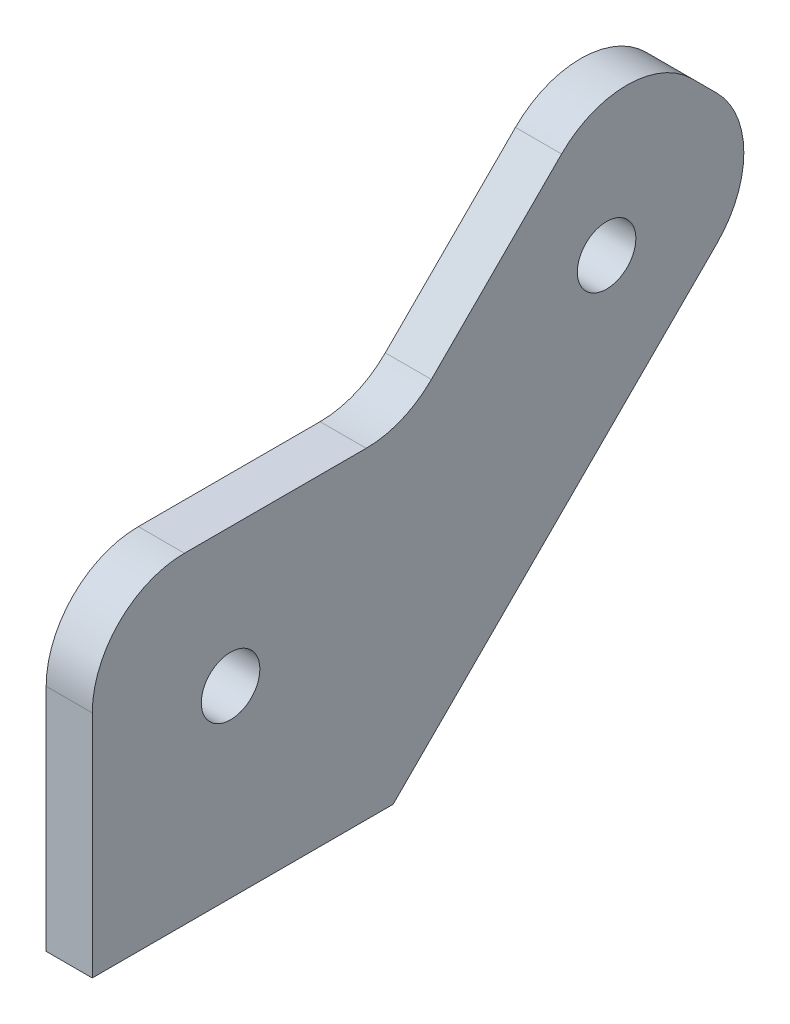
SolidWorks part; units mm, degrees
ref_plane "Front Plane" through (0, 0, 0) normal (0, 0, 1) x (1, 0, 0)
ref_plane "Top Plane" through (0, 0, 0) normal (0, 1, 0) x (1, 0, 0)
ref_plane "Right Plane" through (0, 0, 0) normal (1, 0, 0) x (0, 0, -1)
sketch "Sketch1" plane through (0, 0, 0) normal (1, 0, 0) x (0, 0, -1)
  line L0 (69.9001, 0) -> (-62.5182, 0) construction
  line L1 (-9.5152, 19.93) -> (65.4385, 19.93) construction
  line L2 (-9.5152, 19.93) -> (-9.5152, 56.8817) construction
  line L3 (8.1143, 0) -> (-24.5152, 0)
  line L4 (-24.5152, 0) -> (-24.5152, 24.8988)
  line L5 (-14.5152, 34.8988) -> (5.1919, 34.8988)
  line L6 (12.263, 37.8277) -> (26.3806, 51.9453)
  line L7 (40.5227, 51.9453) -> (43.2201, 49.2479)
  line L8 (43.2201, 35.1058) -> (8.1143, 0)
  line L9 (12.263, 37.8277) -> (24.4131, 37.8277) construction
  line L10 (22.8451, 48.4097) -> (39.6845, 31.5703) construction
  circle A0 centre (31.2648, 39.99) radius 3.175
  circle A1 centre (-9.5152, 19.93) radius 3.175
  arc A2 (-24.5152, 24.8988) -> (-14.5152, 34.8988) centre (-14.5152, 24.8988) cw
  arc A3 (12.263, 37.8277) -> (5.1919, 34.8988) centre (5.1919, 44.8988) cw
  arc A4 (43.2201, 35.1058) -> (43.2201, 49.2479) centre (36.149, 42.1769) ccw
  arc A5 (40.5227, 51.9453) -> (26.3806, 51.9453) centre (33.4517, 44.8742) ccw
  point P26 (31.2648, 39.99)
  dimension "D1" = 6.35
  dimension "D2" = 6.35
  dimension "D6" = 10
  dimension "D7" = 10
  dimension "D8" = 10
  dimension "D3" = 19.93
  dimension "D4" = 40.78
  dimension "D5" = 20.06
  dimension "D9" = 15
  dimension "D10" = 15
  dimension "D11" = 45
extrude "Extrude body" add sketch "Sketch1" along normal blind 5
sketch "Sketch2" plane through (0, 0, 0) normal (1, 0, 0) x (0, 0, -1)
  line L12 (-21.5152, 24.8988) -> (-21.5152, 3)
  line L13 (-21.5152, 3) -> (6.8717, 3)
  line L14 (6.8717, 3) -> (41.0988, 37.2271)
  line L15 (41.0988, 47.1266) -> (38.4014, 49.824)
  line L16 (28.5019, 49.824) -> (14.3843, 35.7064)
  line L17 (5.1919, 31.8988) -> (-14.5152, 31.8988)
  line L18 (-21.5152, 24.8988) -> (-21.5152, 3)
  line L19 (-21.5152, 3) -> (6.8717, 3)
  line L20 (6.8717, 3) -> (41.0988, 37.2271)
  line L21 (41.0988, 47.1266) -> (38.4014, 49.824)
  line L22 (28.5019, 49.824) -> (14.3843, 35.7064)
  line L23 (5.1919, 31.8988) -> (-14.5152, 31.8988)
  arc A8 (-14.5152, 31.8988) -> (-21.5152, 24.8988) centre (-14.5152, 24.8988) ccw
  arc A9 (41.0988, 37.2271) -> (41.0988, 47.1266) centre (36.149, 42.1769) ccw
  arc A10 (38.4014, 49.824) -> (28.5019, 49.824) centre (33.4517, 44.8742) ccw
  arc A11 (5.1919, 31.8988) -> (14.3843, 35.7064) centre (5.1919, 44.8988) ccw
  arc A12 (-14.5152, 31.8988) -> (-21.5152, 24.8988) centre (-14.5152, 24.8988) ccw
  arc A13 (41.0988, 37.2271) -> (41.0988, 47.1266) centre (36.149, 42.1769) ccw
  arc A14 (38.4014, 49.824) -> (28.5019, 49.824) centre (33.4517, 44.8742) ccw
  arc A15 (5.1919, 31.8988) -> (14.3843, 35.7064) centre (5.1919, 44.8988) ccw
  dimension "D1" = 3
extrude "Inset body" cut sketch "Sketch2" along normal blind 2
sketch "Sketch3" plane through (2, 0, 0) normal (-1, 0, 0) x (0, 0, 1)
  circle A0 centre (9.5152, 19.93) radius 6.175
  circle A1 centre (-31.2648, 39.99) radius 6.175
  circle A2 centre (9.5152, 19.93) radius 3.175 construction
  circle A3 centre (-31.2648, 39.99) radius 3.175 construction
  dimension "D1" = 3
  dimension "D2" = 3
extrude "Cut hole boss" add sketch "Sketch3" along normal blind 5
sketch "Ream hole" plane through (0, 0, 0) normal (-1, 0, 0) x (0, 0, 1)
  circle A0 centre (-31.2648, 39.99) radius 3.175
  circle A1 centre (9.5152, 19.93) radius 3.175
extrude "Cut-Extrude2" cut sketch "Ream hole" along normal through all and the other way blind 5
